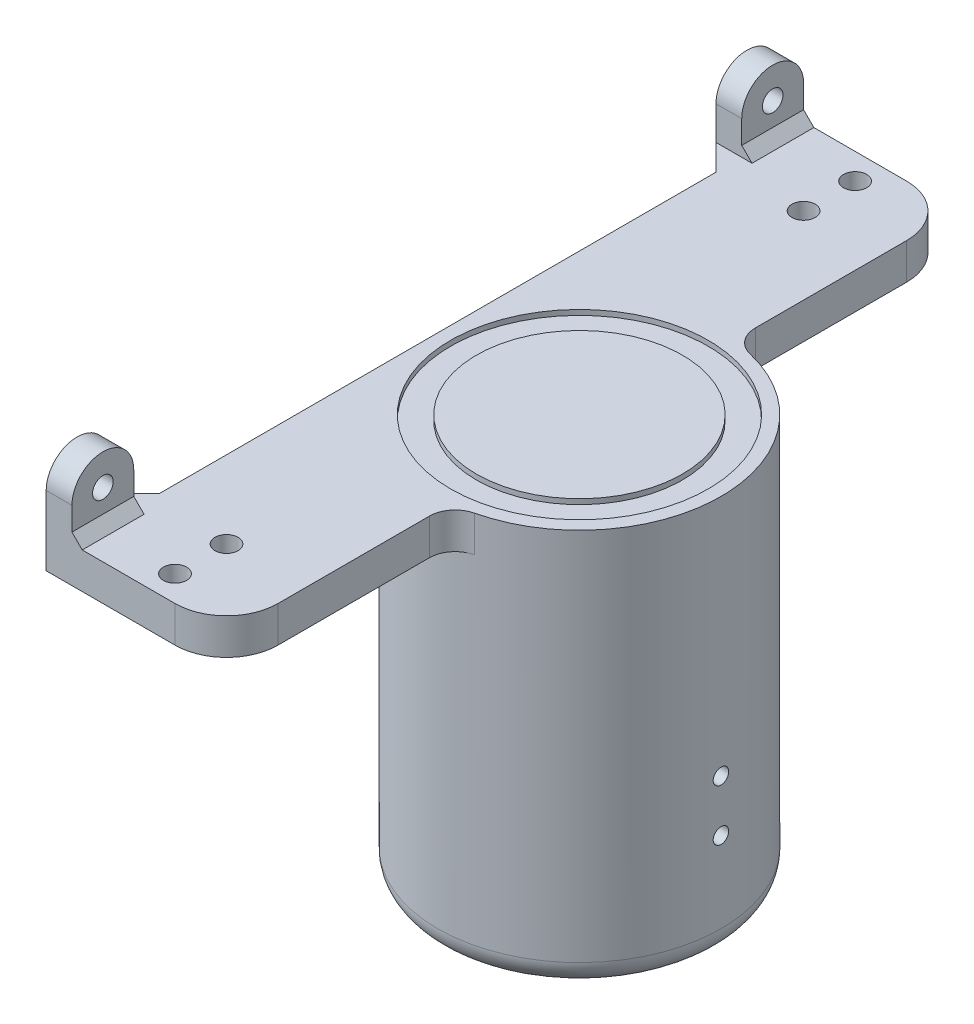
SolidWorks part; units mm, degrees
material "PETG"
ref_plane "Alzado" through (0, 0, 0) normal (0, 0, 1) x (1, 0, 0)
ref_plane "Planta" through (0, 0, 0) normal (0, 1, 0) x (1, 0, 0)
ref_plane "Vista lateral" through (0, 0, 0) normal (1, 0, 0) x (0, 0, -1)
sketch "Croquis1" plane through (0, 0, 0) normal (1, 0, 0) x (0, 0, -1)
  circle A0 centre (-65, 0) radius 3
  circle A1 centre (65, 0) radius 3
  dimension "D3" = 6
  dimension "D4" = 6
  dimension "D1" = 65
  dimension "D2" = 130
extrude "Saliente-Extruir1" add sketch "Croquis1" along normal blind 20
sketch "Croquis2" plane through (20, 0, 0) normal (1, 0, 0) x (0, 0, -1)
  line L5 (71, 3.5) -> (-71, 3.5)
  line L6 (71, 3.5) -> (71, -3.5)
  line L7 (71, -3.5) -> (-71, -3.5)
  line L8 (-71, 3.5) -> (-71, -3.5)
  line L9 (71, 3.5) -> (-71, -3.5) construction
  line L10 (71, -3.5) -> (-71, 3.5) construction
  circle A0 centre (-65, 0) radius 3 construction
  point P0 (0, 0)
  dimension "D2" = 7
  dimension "D1" = 6
extrude "Saliente-Extruir2" add sketch "Croquis2" along normal blind 30
sketch "Croquis3" plane through (0, -3.5, 0) normal (0, -1, 0) x (1, 0, 0)
  line L0 (20, 71) -> (20, -71) construction
  circle A0 centre (47.5, 0) radius 27.5
  dimension "D1" = 55
extrude "Saliente-Extruir3" add sketch "Croquis3" along normal blind 70 and the other way up to surface (7 mm away) other way up to face at (35, 3.5, 0)
sketch "Croquis4" plane through (0, -73.5, 0) normal (0, -1, 0) x (1, 0, 0)
  circle A1 centre (47.5, 0) radius 25
  dimension "D1" = 50
extrude "Cortar-Extruir1" cut sketch "Croquis4" against normal up to surface (70 mm away) up to face at (33.4899, -3.5, -44.0008)
sketch "Croquis5" plane through (0, 0, 0) normal (-1, 0, 0) x (0, 0, 1)
  circle A0 centre (-65, 0) radius 1
  circle A1 centre (65, 0) radius 1
  dimension "D1" = 2
  dimension "D2" = 2
extrude "Cortar-Extruir2" cut sketch "Croquis5" against normal blind 5
sketch "Croquis6" plane through (0, 3.5, 0) normal (0, 1, 0) x (1, 0, 0)
  line L0 (0, 0) -> (75, 0) construction
  line L1 (50, 71) -> (20, 71) construction
  circle A0 centre (35, 66) radius 2.25
  circle A1 centre (35, 56) radius 2.25
  arc A2 (50, -27.3861) -> (50, 27.3861) centre (47.5, 0) ccw construction
  circle A3 centre (35, -66) radius 2.25
  circle A4 centre (35, -56) radius 2.25
  point P12 (35, 71)
  dimension "D1" = 4.5
  dimension "D2" = 4.5
  dimension "D3" = 5
  dimension "D4" = 10
extrude "Cortar-Extruir3" cut sketch "Croquis6" against normal blind 10
fillet "Redondeo1" radius 10 2 edges at (50, 0, 71) (50, 0, -71)
sketch "Croquis7" plane through (20, 0, 0) normal (-1, 0, 0) x (0, 0, 1)
  line L5 (-71, -3.5) -> (0, -3.5)
  line L6 (0, -3.5) -> (71, -3.5)
  line L7 (71, -3.5) -> (71, 3.5)
  line L8 (71, 3.5) -> (-71, 3.5)
  line L9 (-71, 3.5) -> (-71, -3.5)
  line L10 (-71, -3.5) -> (0, -3.5)
  line L11 (0, -3.5) -> (71, -3.5)
  line L12 (71, -3.5) -> (71, 3.5)
  line L13 (71, 3.5) -> (-71, 3.5)
  line L14 (-71, 3.5) -> (-71, -3.5)
  dimension "D1" = 0
extrude "Cortar-Extruir4" cut sketch "Croquis7" along normal through all
sketch "Croquis8" plane through (20, 0, 0) normal (-1, 0, 0) x (0, 0, 1)
  line L0 (-71, 10) -> (-71, -3.5)
  line L2 (-59, 10) -> (-59, -3.5)
  line L3 (0, -3.5) -> (-71, -3.5) construction
  line L4 (0, 0) -> (0, 3.5) construction
  line L5 (-71, 3.5) -> (71, 3.5) construction
  line L6 (-59, -3.5) -> (-71, -3.5)
  line L7 (-71, -3.5) -> (-71, 3.5) construction
  line L8 (59, 10) -> (59, -3.5)
  line L9 (59, -3.5) -> (71, -3.5)
  line L10 (71, 10) -> (71, -3.5)
  arc A0 (-59, 10) -> (-71, 10) centre (-65, 10) ccw
  circle A3 centre (-65, 10) radius 2
  arc A4 (-71, 10) -> (-59, 10) centre (-65, 10) ccw construction
  arc A5 (59, 10) -> (71, 10) centre (65, 10) cw
  circle A6 centre (65, 10) radius 2
  dimension "D1" = 12
  dimension "D2" = 10
  dimension "D4" = 4
extrude "Saliente-Extruir4" add sketch "Croquis8" along normal blind 5
fillet "Redondeo3" radius 5 3 edges at (47.5, -73.5, -27.5) (50, 0, -27.3861) (50, 0, 27.3861)
chamfer "Chaflán2" distance 5 angle 45 2 edges at (20, 0, 59) (20, 0, -59)
chamfer "Chaflán1" distance 2 angle 45 2 edges at (20, 3.5, -65) (20, 3.5, 65)
sketch "Croquis9" plane through (50, 0, 0) normal (1, 0, 0) x (0, 0, -1)
  line L0 (25, -73.5) -> (-25, -73.5) construction
  circle A0 centre (0, -53.5) radius 1.5
  circle A1 centre (0, -43.5) radius 1.5
  dimension "D1" = 3
  dimension "D2" = 3
  dimension "D3" = 10
  dimension "D4" = 20
extrude "Cortar-Extruir5" cut sketch "Croquis9" along normal through all
sketch "Croquis10" plane through (0, 3.5, 0) normal (0, 1, 0) x (1, 0, 0)
  circle A0 centre (47.5, 0) radius 25
  circle A1 centre (47.5, 0) radius 20
  dimension "D1" = 50
  dimension "D2" = 40
extrude "Cortar-Extruir6" cut sketch "Croquis10" against normal blind 1
